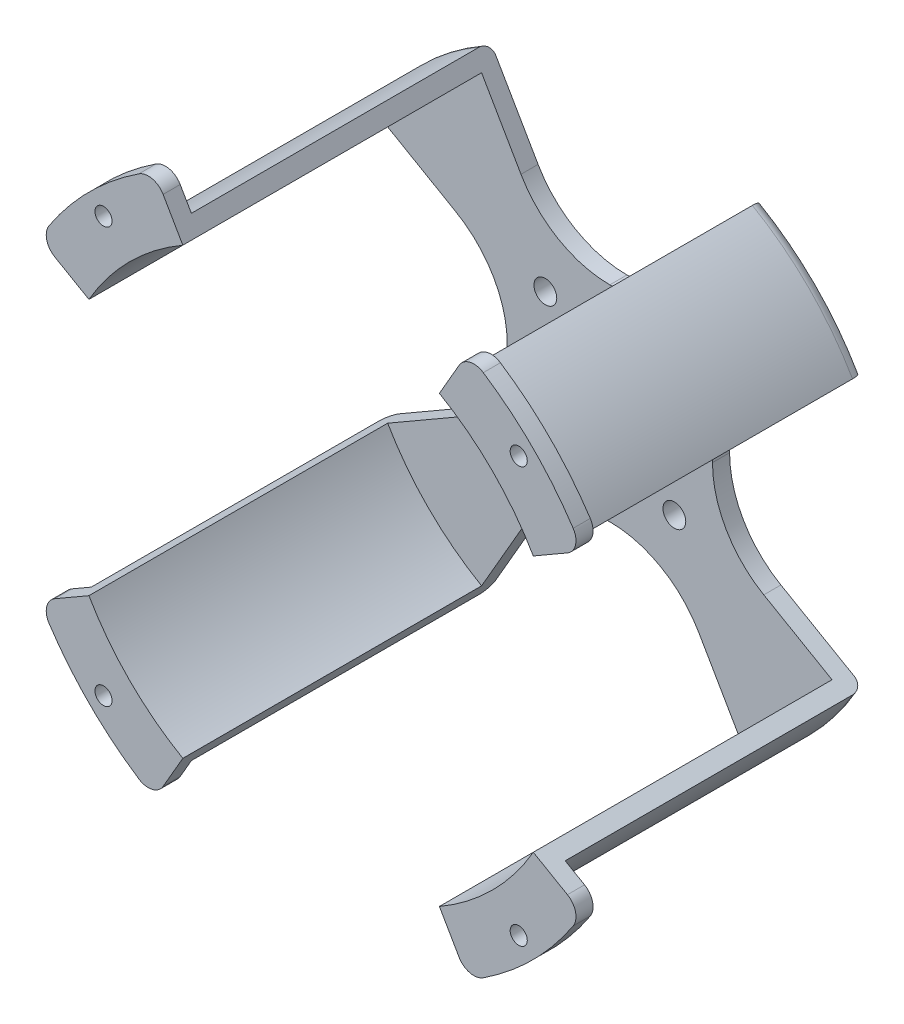
SolidWorks part; units mm, degrees
material "1060 合金"
ref_plane "前视基准面" through (0, 0, 0) normal (0, 0, 1) x (1, 0, 0)
ref_plane "上视基准面" through (0, 0, 0) normal (0, 1, 0) x (1, 0, 0)
ref_plane "右视基准面" through (0, 0, 0) normal (1, 0, 0) x (0, 0, -1)
sketch "草图1" plane through (0, 0, 0) normal (0, 0, 1) x (1, 0, 0)
  line L0 (0, 0) -> (33.9411, 33.9411) construction
  line L1 (10.4339, 10.4339) -> (13.2623, 7.6055) construction
  line L4 (15.2381, -9.5812) -> (36.6515, -30.9946)
  line L7 (9.5812, -15.2381) -> (30.9946, -36.6515)
  line L10 (15.2381, 9.5812) -> (36.6515, 30.9946)
  line L11 (9.5812, 15.2381) -> (30.9946, 36.6515)
  line L12 (-9.5812, -15.2381) -> (-30.9946, -36.6515)
  line L13 (-15.2381, -9.5812) -> (-36.6515, -30.9946)
  line L14 (-15.2381, 9.5812) -> (-36.6515, 30.9946)
  line L15 (-9.5812, 15.2381) -> (-30.9946, 36.6515)
  circle A2 centre (0, 0) radius 12
  arc A3 (9.5812, 15.2381) -> (-9.5812, 15.2381) centre (0, 0) ccw
  arc A4 (-15.2381, 9.5812) -> (-15.2381, -9.5812) centre (0, 0) ccw
  arc A5 (-9.5812, -15.2381) -> (9.5812, -15.2381) centre (0, 0) ccw
  arc A6 (15.2381, -9.5812) -> (15.2381, 9.5812) centre (0, 0) ccw
  arc A8 (-30.9946, 36.6515) -> (-36.6515, 30.9946) centre (0, 0) ccw
  arc A14 (36.6515, 30.9946) -> (30.9946, 36.6515) centre (0, 0) ccw
  arc A15 (30.9946, -36.6515) -> (36.6515, -30.9946) centre (0, 0) ccw
  arc A16 (-36.6515, -30.9946) -> (-30.9946, -36.6515) centre (0, 0) ccw
  point P27 (0, 0)
  point P41 (0, 0)
  dimension "D1" = 4
extrude "凸台-拉伸1" add sketch "草图1" along normal blind 3
sketch "草图2" plane through (0, 0, 3) normal (0, 0, 1) x (1, 0, 0)
  line L12 (-15.2381, -9.5812) -> (-36.6515, -30.9946) construction
  line L13 (-30.9946, -36.6515) -> (-9.5812, -15.2381) construction
  line L14 (9.5812, -15.2381) -> (30.9946, -36.6515) construction
  line L15 (36.6515, -30.9946) -> (15.2381, -9.5812) construction
  line L16 (15.2381, 9.5812) -> (36.6515, 30.9946) construction
  line L17 (30.9946, 36.6515) -> (9.5812, 15.2381) construction
  line L18 (-36.6515, 30.9946) -> (-15.2381, 9.5812) construction
  line L19 (-9.5812, 15.2381) -> (-30.9946, 36.6515) construction
  line L20 (-34.5223, -28.8654) -> (-36.6515, -30.9946)
  line L21 (-30.9946, -36.6515) -> (-28.8654, -34.5223)
  line L22 (28.8654, -34.5223) -> (30.9946, -36.6515)
  line L23 (36.6515, -30.9946) -> (34.5223, -28.8654)
  line L24 (34.5223, 28.8654) -> (36.6515, 30.9946)
  line L25 (30.9946, 36.6515) -> (28.8654, 34.5223)
  line L26 (-36.6515, 30.9946) -> (-34.5223, 28.8654)
  line L27 (-28.8654, 34.5223) -> (-30.9946, 36.6515)
  arc A0 (31.7534, 35.9961) -> (30.9946, 36.6515) centre (0, 0) ccw
  arc A1 (-29.6277, 33.8703) -> (-34.5223, 28.8654) centre (0, 0) ccw
  arc A2 (-35.9961, 31.7534) -> (-36.6515, 30.9946) centre (0, 0) ccw
  arc A3 (-33.8703, -29.6277) -> (-28.8654, -34.5223) centre (0, 0) ccw
  arc A4 (29.6277, -33.8703) -> (33.8703, -29.6277) centre (0, 0) ccw
  arc A5 (-31.7534, -35.9961) -> (-30.9946, -36.6515) centre (0, 0) ccw
  arc A6 (35.9961, -31.7534) -> (36.6515, -30.9946) centre (0, 0) ccw
  arc A7 (33.8703, -29.6277) -> (34.5223, -28.8654) centre (0, 0) ccw
  arc A8 (36.6515, 30.9946) -> (31.7534, 35.9961) centre (0, 0) ccw
  arc A9 (34.5223, 28.8654) -> (28.8654, 34.5223) centre (0, 0) ccw
  arc A10 (30.9946, -36.6515) -> (35.9961, -31.7534) centre (0, 0) ccw
  arc A11 (28.8654, -34.5223) -> (29.6277, -33.8703) centre (0, 0) ccw
  arc A12 (-36.6515, -30.9946) -> (-31.7534, -35.9961) centre (0, 0) ccw
  arc A13 (-34.5223, -28.8654) -> (-33.8703, -29.6277) centre (0, 0) ccw
  arc A14 (-30.9946, 36.6515) -> (-35.9961, 31.7534) centre (0, 0) ccw
  arc A15 (-28.8654, 34.5223) -> (-29.6277, 33.8703) centre (0, 0) ccw
  point P23 (0, 0)
extrude "凸台-拉伸2" add sketch "草图2" along normal blind 52.4
sketch "草图3" plane through (0, 0, 55.4) normal (0, 0, 1) x (1, 0, 0)
  line L0 (-34.5223, -28.8654) -> (-36.6515, -30.9946) construction
  line L1 (-30.9946, -36.6515) -> (-28.8654, -34.5223) construction
  line L2 (36.6515, -30.9946) -> (34.5223, -28.8654)
  line L3 (41.6163, -35.9595) -> (34.5223, -28.8654)
  line L6 (28.8654, -34.5223) -> (30.9946, -36.6515) construction
  line L7 (34.5223, 28.8654) -> (36.6515, 30.9946) construction
  line L10 (30.9946, 36.6515) -> (28.8654, 34.5223) construction
  line L11 (-36.6515, 30.9946) -> (-34.5223, 28.8654) construction
  line L14 (-28.8654, 34.5223) -> (-30.9946, 36.6515) construction
  line L15 (-34.5223, -28.8654) -> (-41.6163, -35.9595)
  line L18 (28.8654, -34.5223) -> (30.9946, -36.6515)
  line L19 (-35.9595, -41.6163) -> (-28.8654, -34.5223)
  line L20 (28.8654, -34.5223) -> (35.9595, -41.6163)
  line L21 (34.5223, 28.8654) -> (41.6163, 35.9595)
  line L22 (35.9595, 41.6163) -> (28.8654, 34.5223)
  line L23 (-41.6163, 35.9595) -> (-34.5223, 28.8654)
  line L24 (-28.8654, 34.5223) -> (-35.9595, 41.6163)
  arc A2 (28.8654, -34.5223) -> (34.5223, -28.8654) centre (0, 0) ccw
  arc A3 (30.9946, -36.6515) -> (36.6515, -30.9946) centre (0, 0) ccw
  arc A6 (-35.9595, 41.6163) -> (-41.6163, 35.9595) centre (0, 0) ccw
  arc A7 (-28.8654, 34.5223) -> (-34.5223, 28.8654) centre (0, 0) ccw
  arc A10 (41.6163, 35.9595) -> (35.9595, 41.6163) centre (0, 0) ccw
  arc A11 (34.5223, 28.8654) -> (28.8654, 34.5223) centre (0, 0) ccw
  arc A14 (35.9595, -41.6163) -> (41.6163, -35.9595) centre (0, 0) ccw
  arc A15 (28.8654, -34.5223) -> (34.5223, -28.8654) centre (0, 0) ccw
  arc A24 (-41.6163, -35.9595) -> (-35.9595, -41.6163) centre (0, 0) ccw
  arc A25 (-34.5223, -28.8654) -> (-28.8654, -34.5223) centre (0, 0) ccw
  dimension "D1" = 0
extrude "凸台-拉伸3" add sketch "草图3" against normal blind 3
sketch "草图4" plane through (0, 0, 0) normal (0, 0, -1) x (-1, 0, 0)
  line L0 (0, 0) -> (11.3137, 11.3137) construction
  circle A0 centre (0, 0) radius 15 construction
  circle A1 centre (0, 0) radius 16 construction
  circle A6 centre (11.3137, 11.3137) radius 2
  circle A7 centre (11.3137, -11.3137) radius 2
  circle A8 centre (-11.3137, -11.3137) radius 2
  circle A9 centre (-11.3137, 11.3137) radius 2
  point P15 (0, 0)
  point P24 (0, 0)
  dimension "D2" = 4
fillet "圆角1" radius 10 8 edges at (-15.2381, 9.5812, 1.5) (-15.2381, -9.5812, 1.5) (-9.5812, -15.2381, 1.5) (9.5812, -15.2381, 1.5) (15.2381, -9.5812, 1.5) (15.2381, 9.5812, 1.5) (-9.5812, 15.2381, 1.5) (9.5812, 15.2381, 1.5)
sketch "草图8" plane through (0, 0, 52.4) normal (0, 0, -1) x (-1, 0, 0)
  line L0 (0, 0) -> (36.416, 36.416) construction
  circle A0 centre (0, 0) radius 51.5 construction
  circle A1 centre (36.416, 36.416) radius 1.5
  circle A2 centre (36.416, -36.416) radius 1.5
  circle A3 centre (-36.416, -36.416) radius 1.5
  circle A4 centre (-36.416, 36.416) radius 1.5
  point P14 (0, 0)
  dimension "D1" = 4
extrude "切除-拉伸2" cut sketch "草图8" against normal blind 32
fillet "圆角3" radius 3 4 edges at (33.9411, -33.9411, 0) (-33.9411, 33.9411, 0) (33.9411, 33.9411, 0) (-33.9411, -33.9411, 0)
extrude "切除-拉伸3" cut sketch "草图4" against normal blind 4
sketch "草图10" plane through (0, 0, 0) normal (0, 0, -1) x (-1, 0, 0)
  circle A0 centre (0, 0) radius 18
  circle A1 centre (0, 0) radius 45
extrude "凸台-拉伸6" add sketch "草图10" against normal blind 3
sketch "草图11" plane through (0, 0, 0) normal (0, 0, -1) x (-1, 0, 0)
  circle A0 centre (0, 0) radius 45
  circle A1 centre (0, 0) radius 48
extrude "凸台-拉伸7" add sketch "草图11" against normal up to surface (52.4 mm away) up to face at (34.916, 36.416, 52.4)
sketch "草图12" plane through (0, 0, 52.4) normal (0, 0, 1) x (1, 0, 0)
  circle A0 centre (0, 0) radius 48
  circle A1 centre (0, 0) radius 45
extrude "凸台-拉伸8" add sketch "草图12" along normal blind 3
sketch "草图13" plane through (0, 0, 0) normal (0, 0, -1) x (-1, 0, 0)
  line L1 (0, 18) -> (0, 48) construction
  line L10 (9, 15.5885) -> (24, 41.5692)
  line L11 (15.5885, 9) -> (41.5692, 24)
  line L12 (15.5885, -9) -> (41.5692, -24)
  line L13 (9, -15.5885) -> (24, -41.5692)
  line L14 (-9, -15.5885) -> (-24, -41.5692)
  line L15 (-15.5885, -9) -> (-41.5692, -24)
  line L16 (-15.5885, 9) -> (-41.5692, 24)
  line L17 (-9, 15.5885) -> (-24, 41.5692)
  arc A0 (-15.5885, 9) -> (-15.5885, -9) centre (0, 0) ccw
  arc A1 (-41.5692, 24) -> (-41.5692, -24) centre (0, 0) ccw
  arc A2 (9, 15.5885) -> (-9, 15.5885) centre (0, 0) ccw
  arc A3 (24, 41.5692) -> (-24, 41.5692) centre (0, 0) ccw
  arc A4 (41.5692, -24) -> (41.5692, 24) centre (0, 0) ccw
  arc A5 (15.5885, -9) -> (15.5885, 9) centre (0, 0) ccw
  arc A6 (-9, -15.5885) -> (9, -15.5885) centre (0, 0) ccw
  arc A7 (-24, -41.5692) -> (24, -41.5692) centre (0, 0) ccw
  circle A10 centre (0, 0) radius 48 construction
  point P16 (0, 0)
  point P39 (0, 0)
  dimension "D4" = 4
extrude "切除-拉伸4" cut sketch "草图13" against normal blind 68
fillet "圆角4" radius 18 8 edges at (15.5885, -9, 1.5) (15.5885, 9, 1.5) (9, -15.5885, 1.5) (-9, -15.5885, 1.5) (-15.5885, -9, 1.5) (-15.5885, 9, 1.5) (-9, 15.5885, 1.5) (9, 15.5885, 1.5)
sketch "草图14" plane through (0, 0, 55.4) normal (0, 0, 1) x (1, 0, 0)
  line L2 (-36.6515, -30.9946) -> (-41.6163, -35.9595) construction
  line L3 (-35.9595, -41.6163) -> (-30.9946, -36.6515) construction
  line L6 (30.9946, -36.6515) -> (35.9595, -41.6163) construction
  line L7 (41.6163, -35.9595) -> (36.6515, -30.9946) construction
  line L9 (36.6515, 30.9946) -> (41.6163, 35.9595) construction
  line L10 (35.9595, 41.6163) -> (30.9946, 36.6515) construction
  line L14 (-41.6163, 35.9595) -> (-36.6515, 30.9946) construction
  line L15 (-30.9946, 36.6515) -> (-35.9595, 41.6163) construction
  line L18 (-36.6515, -30.9946) -> (-41.6163, -35.9595)
  line L19 (-35.9595, -41.6163) -> (-30.9946, -36.6515)
  line L22 (30.9946, -36.6515) -> (35.9595, -41.6163)
  line L23 (41.6163, -35.9595) -> (36.6515, -30.9946)
  line L25 (36.6515, 30.9946) -> (41.6163, 35.9595)
  line L26 (35.9595, 41.6163) -> (30.9946, 36.6515)
  line L30 (-41.6163, 35.9595) -> (-36.6515, 30.9946)
  line L31 (-30.9946, 36.6515) -> (-35.9595, 41.6163)
  line L32 (-41.5692, -24) -> (-38.9711, -22.5) construction
  line L33 (-22.5, -38.9711) -> (-24, -41.5692) construction
  line L34 (24, -41.5692) -> (22.5, -38.9711) construction
  line L35 (38.9711, -22.5) -> (41.5692, -24) construction
  line L36 (-38.9711, 22.5) -> (-41.5692, 24) construction
  line L37 (-24, 41.5692) -> (-22.5, 38.9711) construction
  line L38 (41.5692, 24) -> (38.9711, 22.5) construction
  line L39 (22.5, 38.9711) -> (24, 41.5692) construction
  line L40 (-47.6314, -27.5) -> (-41.5692, -24)
  line L41 (-24, -41.5692) -> (-27.5, -47.6314)
  line L42 (27.5, -47.6314) -> (24, -41.5692)
  line L43 (41.5692, -24) -> (47.6314, -27.5)
  line L44 (-41.5692, 24) -> (-47.6314, 27.5)
  line L45 (-27.5, 47.6314) -> (-24, 41.5692)
  line L46 (47.6314, 27.5) -> (41.5692, 24)
  line L47 (24, 41.5692) -> (27.5, 47.6314)
  arc A0 (-27.5, 47.6314) -> (-35.9595, 41.6163) centre (0, 0) ccw
  arc A1 (-24, 41.5692) -> (-30.9946, 36.6515) centre (0, 0) ccw
  arc A2 (41.5692, 24) -> (36.6515, 30.9946) centre (0, 0) ccw
  arc A3 (47.6314, 27.5) -> (41.6163, 35.9595) centre (0, 0) ccw
  arc A4 (27.5, -47.6314) -> (35.9595, -41.6163) centre (0, 0) ccw
  arc A5 (24, -41.5692) -> (30.9946, -36.6515) centre (0, 0) ccw
  arc A6 (-41.5692, -24) -> (-36.6515, -30.9946) centre (0, 0) ccw
  arc A7 (-47.6314, -27.5) -> (-41.6163, -35.9595) centre (0, 0) ccw
  arc A8 (-36.6515, 30.9946) -> (-41.5692, 24) centre (0, 0) ccw
  arc A9 (-41.6163, 35.9595) -> (-47.6314, 27.5) centre (0, 0) ccw
  arc A10 (30.9946, 36.6515) -> (24, 41.5692) centre (0, 0) ccw
  arc A11 (35.9595, 41.6163) -> (27.5, 47.6314) centre (0, 0) ccw
  arc A12 (36.6515, -30.9946) -> (41.5692, -24) centre (0, 0) ccw
  arc A13 (41.6163, -35.9595) -> (47.6314, -27.5) centre (0, 0) ccw
  arc A14 (-30.9946, -36.6515) -> (-24, -41.5692) centre (0, 0) ccw
  arc A15 (-35.9595, -41.6163) -> (-27.5, -47.6314) centre (0, 0) ccw
extrude "凸台-拉伸9" add sketch "草图14" against normal blind 3
fillet "圆角5" radius 3 8 edges at (-27.5, 47.6314, 53.9) (27.5, -47.6314, 53.9) (47.6314, -27.5, 53.9) (-47.6314, 27.5, 53.9) (47.6314, 27.5, 53.9) (-47.6314, -27.5, 53.9) (27.5, 47.6314, 53.9) (-27.5, -47.6314, 53.9)
fillet "圆角6" radius 2 1 edges at (-33.9411, -33.9411, 0)
sketch "草图17" plane through (0, 0, 0) normal (0, 0, -1) x (-1, 0, 0)
  circle A0 centre (0, 0) radius 12
  circle A1 centre (0, 0) radius 11
  dimension "D1" = 22
extrude "凸台-拉伸10" add sketch "草图17" against normal blind 3
